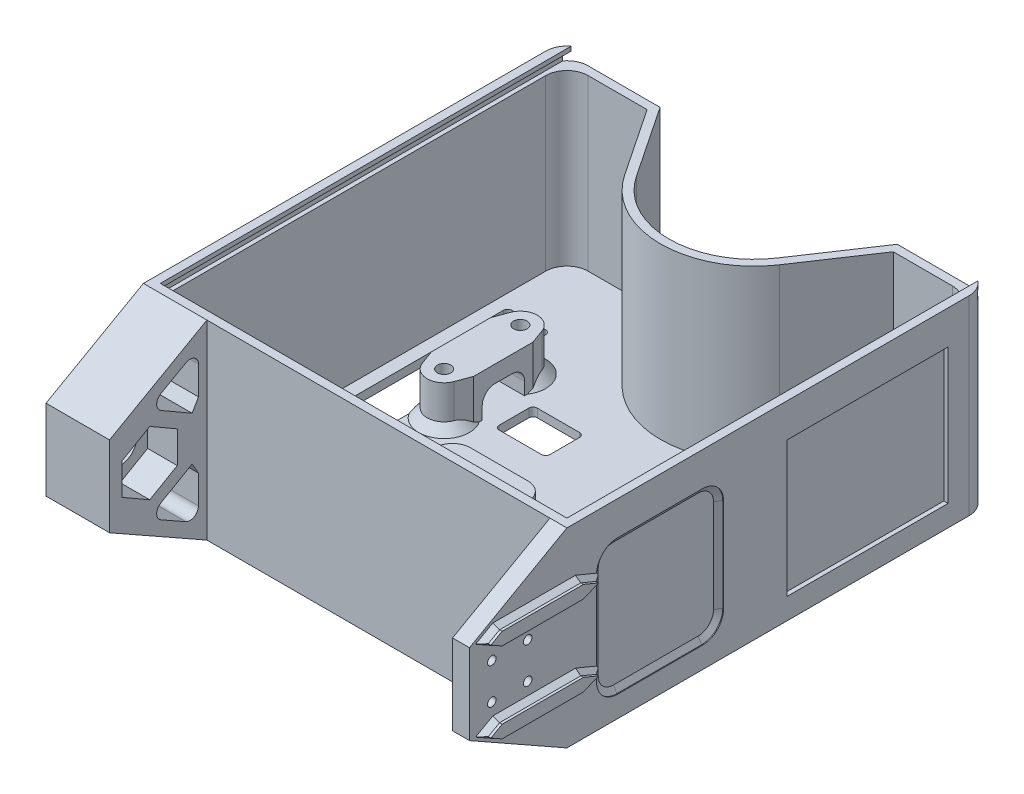
SolidWorks part; units mm, degrees
material "PVC hart"
ref_plane "Ebene vorne" through (0, 0, 0) normal (0, 0, 1) x (1, 0, 0)
ref_plane "Ebene oben" through (0, 0, 0) normal (0, 1, 0) x (1, 0, 0)
ref_plane "Ebene rechts" through (0, 0, 0) normal (1, 0, 0) x (0, 0, -1)
sketch "Grundplatte" plane through (0, 0, 0) normal (0, 1, 0) x (1, 0, 0)
  line L0 (0, 69.0751) -> (0, -94.5087) construction
  line L2 (-50, 50) -> (-50, -50)
  line L3 (-50, -50) -> (50, -50)
  line L4 (50, 50) -> (50, -50)
  line L5 (-50, 50) -> (50, -50) construction
  line L6 (-50, -50) -> (50, 50) construction
  line L7 (-50, 50) -> (-28, 50)
  line L8 (-28, 50) -> (-16.6199, 33)
  line L9 (28, 50) -> (16.6199, 33)
  line L10 (50, 50) -> (28, 50)
  arc A0 (-16.6199, 33) -> (16.6199, 33) centre (0, 44.1257) ccw
  point P0 (0, 0)
  dimension "D4" = 20
  dimension "D1" = 100
  dimension "D2" = 100
  dimension "D3" = 22
  dimension "D5" = 17
extrude "Aufsatz-Linear austragen1" add sketch "Grundplatte" along normal blind 45
shell "Wandung1" thickness 2 removed face at (0, 45, -19.6407)
sketch "Skizze1" plane through (0, 2, 0) normal (0, 1, 0) x (1, 0, 0)
  line L0 (0, 51.8201) -> (0, -55.3816) construction
  line L1 (-28, 50) -> (-50, 50) construction
  line L2 (-45, 31) -> (-35, 31)
  line L3 (-45, 31) -> (-45, -11)
  line L4 (-45, -11) -> (-35, -11)
  line L5 (-35, 31) -> (-35, -11)
  line L6 (-45, 31) -> (-35, -11) construction
  line L7 (-45, -11) -> (-35, 31) construction
  line L8 (50, 50) -> (28, 50) construction
  line L9 (35, 31) -> (45, 31)
  line L10 (35, 31) -> (35, -11)
  line L11 (35, -11) -> (45, -11)
  line L12 (45, 31) -> (45, -11)
  line L13 (35, 31) -> (45, -11) construction
  line L14 (35, -11) -> (45, 31) construction
  point P3 (-40, 10)
  point P10 (40, 10)
  dimension "D1" = 10
  dimension "D2" = 42
  dimension "D3" = 40
  dimension "D4" = 40
  dimension "D5" = 42
  dimension "D6" = 10
  dimension "D7" = 40
  dimension "D8" = 40
extrude "Schnitt-Linear austragen1" cut sketch "Skizze1" against normal up to surface (2 mm away) up to face at (0, 0, -19.6407)
sketch "Skizze2" plane through (0, 2, 0) normal (0, 1, 0) x (1, 0, 0)
  line L20 (-65.457, 10) -> (65.6069, 10) construction
  line L21 (0, 51.8201) -> (0, -54.6693) construction
  line L22 (-35, -11) -> (-35, 31) construction
  line L24 (-35, 16) -> (-35, 4)
  line L26 (-25, 16) -> (-25, 4)
  line L27 (-35, 16) -> (-25, 4) construction
  line L28 (-35, 4) -> (-25, 16) construction
  line L33 (35, 16) -> (35, 17)
  line L34 (33.7533, 20.3831) -> (35, 17)
  line L36 (-35, 16) -> (-35, 17)
  line L37 (-25, 16) -> (-25, 17)
  line L38 (-35, 4) -> (-35, 3)
  line L39 (-25, 4) -> (-25, 3)
  line L40 (-26.2467, 20.3831) -> (-25, 17)
  line L41 (-33.7533, 20.3831) -> (-35, 17)
  line L42 (-26.2467, -0.3831) -> (-25, 3)
  line L43 (-33.7533, -0.3831) -> (-35, 3)
  line L44 (26.2467, 20.3831) -> (25, 17)
  line L45 (25, 16) -> (25, 17)
  line L46 (25, 16) -> (25, 4)
  line L47 (25, 4) -> (25, 3)
  line L48 (26.2467, -0.3831) -> (25, 3)
  line L49 (33.7533, -0.3831) -> (35, 3)
  line L50 (35, 4) -> (35, 3)
  line L51 (35, 16) -> (35, 4)
  circle A4 centre (-30, 19) radius 1.6
  circle A5 centre (-30, 1) radius 1.6
  arc A6 (-26.2467, 20.3831) -> (-33.7533, 20.3831) centre (-30, 19) ccw
  arc A7 (-26.2467, -0.3831) -> (-33.7533, -0.3831) centre (-30, 1) cw
  circle A8 centre (30, 1) radius 1.6
  circle A9 centre (30, 19) radius 1.6
  arc A10 (26.2467, 20.3831) -> (33.7533, 20.3831) centre (30, 19) cw
  arc A11 (26.2467, -0.3831) -> (33.7533, -0.3831) centre (30, 1) ccw
  point P4 (-30, 10)
  point P9 (30, 10)
  dimension "D9" = 3.2
  dimension "D10" = 3.2
  dimension "D13" = 4
  dimension "D14" = 4
  dimension "D2" = 30
  dimension "D3" = 10
  dimension "D5" = 1
  dimension "D6" = 1
  dimension "D7" = 1
  dimension "D8" = 1
  dimension "D11" = 9
  dimension "D12" = 9
extrude "Aufsatz-Linear austragen2" add sketch "Skizze2" along normal blind 10
fillet "Verrundung1" radius 1 8 edges at (35, 1, -31) (45, 1, -31) (35, 1, 11) (45, 1, 11) (-35, 1, 11) (-45, 1, 11) (-45, 1, -31) (-35, 1, -31)
sketch "Skizze6" plane through (0, 12, 0) normal (0, 1, 0) x (1, 0, 0)
  circle A0 centre (-30, 19) radius 1.6
  circle A1 centre (-30, 1) radius 1.6
  circle A2 centre (30, 19) radius 1.6
  circle A3 centre (30, 1) radius 1.6
  dimension "D1" = 3.2
  dimension "D2" = 3.2
  dimension "D3" = 3.2
  dimension "D4" = 3.2
extrude "Schnitt-Linear austragen2" cut sketch "Skizze6" against normal through all
sketch "Skizze7" plane through (0, 0, 0) normal (0, -1, 0) x (1, 0, 0)
  line L0 (0, 58.5427) -> (0, -57.727) construction
  line L1 (-26.7091, -1) -> (-28.3546, 1.85)
  line L2 (-28.3546, 1.85) -> (-31.6454, 1.85)
  line L3 (-31.6454, 1.85) -> (-33.2909, -1)
  line L4 (-33.2909, -1) -> (-31.6454, -3.85)
  line L5 (-31.6454, -3.85) -> (-28.3546, -3.85)
  line L6 (-28.3546, -3.85) -> (-26.7091, -1)
  line L7 (28.3546, -21.85) -> (26.7091, -19)
  line L8 (-26.7091, -19) -> (-28.3546, -16.15)
  line L9 (-28.3546, -16.15) -> (-31.6454, -16.15)
  line L10 (-31.6454, -16.15) -> (-33.2909, -19)
  line L11 (-33.2909, -19) -> (-31.6454, -21.85)
  line L12 (-31.6454, -21.85) -> (-28.3546, -21.85)
  line L13 (-28.3546, -21.85) -> (-26.7091, -19)
  line L14 (31.6454, -21.85) -> (28.3546, -21.85)
  line L15 (33.2909, -19) -> (31.6454, -21.85)
  line L16 (31.6454, -16.15) -> (33.2909, -19)
  line L17 (28.3546, -16.15) -> (31.6454, -16.15)
  line L18 (26.7091, -19) -> (28.3546, -16.15)
  line L19 (28.3546, -3.85) -> (26.7091, -1)
  line L20 (31.6454, -3.85) -> (28.3546, -3.85)
  line L21 (33.2909, -1) -> (31.6454, -3.85)
  line L22 (31.6454, 1.85) -> (33.2909, -1)
  line L23 (28.3546, 1.85) -> (31.6454, 1.85)
  line L24 (26.7091, -1) -> (28.3546, 1.85)
  circle A0 centre (-30, -1) radius 2.85 construction
  circle A1 centre (-30, -19) radius 2.85 construction
  dimension "D1" = 5.7
  dimension "D2" = 5.7
extrude "Schnitt-Linear austragen3" cut sketch "Skizze7" against normal offset from surface (9 mm away) 3 up to face at (30, 12, -2.6)
chamfer "Fase1" distance 2 angle 45 8 edges at (34.3766, 2, -1.3084) (30, 2, 3) (34.3766, 2, -18.6916) (30, 2, -23) (-34.3766, 2, -18.6916) (-30, 2, -23) (-34.3766, 2, -1.3084) (-30, 2, 3)
sketch "Skizze8" plane through (0, 0, 0) normal (0, -1, 0) x (1, 0, 0)
  line L0 (0, 60.6503) -> (0, -60.3099) construction
  line L1 (22, -5) -> (10, -5)
  line L2 (-22, -14) -> (-10, -14)
  line L3 (-22, -14) -> (-22, -5)
  line L4 (-22, -5) -> (-10, -5)
  line L5 (-10, -14) -> (-10, -5)
  line L10 (10, -14) -> (10, -5)
  line L11 (22, -14) -> (10, -14)
  line L12 (22, -14) -> (22, -5)
  circle A0 centre (-30, -1) radius 1.6 construction
  dimension "D2" = 4
  dimension "D1" = 12
  dimension "D3" = 10
  dimension "D4" = 9
extrude "Schnitt-Linear austragen4" cut sketch "Skizze8" against normal up to surface (2 mm away) up to face at (-36.1139, 2, -10)
fillet "Verrundung2" radius 1 8 edges at (-22, 1, -14) (-22, 1, -5) (-10, 1, -5) (-10, 1, -14) (22, 1, -14) (22, 1, -5) (10, 1, -14) (10, 1, -5)
fillet "Verrundung3" radius 5 2 edges at (-50, 22.5, -50) (50, 22.5, -50)
fillet "Verrundung4" radius 5 2 edges at (48, 23.5, -48) (-48, 23.5, -48)
sketch "Skizze9" plane through (0, 0, 0) normal (0, -1, 0) x (1, 0, 0)
  line L0 (0, 55.7734) -> (0, -61.0444) construction
  line L1 (-11, -5) -> (-21, -5) construction
  line L2 (-6.8, 43) -> (6.8, 43)
  line L3 (-8, 41.8) -> (-8, 20.2)
  line L4 (-6.8, 19) -> (6.8, 19)
  line L5 (8, 41.8) -> (8, 20.2)
  line L6 (-8, 43) -> (8, 19) construction
  line L7 (-8, 19) -> (8, 43) construction
  arc A0 (6.8, 19) -> (8, 20.2) centre (6.8, 20.2) ccw
  arc A1 (-8, 20.2) -> (-6.8, 19) centre (-6.8, 20.2) ccw
  arc A2 (-6.8, 43) -> (-8, 41.8) centre (-6.8, 41.8) ccw
  arc A3 (6.8, 43) -> (8, 41.8) centre (6.8, 41.8) cw
  point P3 (0, 31)
  dimension "D4" = 1.2
  dimension "D1" = 24
  dimension "D2" = 16
  dimension "D3" = 36
extrude "Schnitt-Linear austragen5" cut sketch "Skizze9" against normal up to next
sketch "Skizze11" plane through (0, 2, 0) normal (0, 1, 0) x (1, 0, 0)
  line L25 (-6.8, -46) -> (6.8, -46)
  line L26 (-11, -20.2) -> (-11, -41.8)
  line L27 (11, -41.8) -> (11, -20.2)
  line L28 (6.8, -16) -> (-6.8, -16)
  line L29 (-6.8, -46) -> (6.8, -46)
  line L30 (-11, -20.2) -> (-11, -41.8)
  line L31 (11, -41.8) -> (11, -20.2)
  line L32 (6.8, -16) -> (-6.8, -16)
  line L62 (-8, -20.2) -> (-8, -41.8)
  line L63 (-6.8, -43) -> (6.8, -43)
  line L64 (8, -41.8) -> (8, -20.2)
  line L65 (-6.8, -19) -> (6.8, -19)
  arc A19 (6.8, -46) -> (11, -41.8) centre (6.8, -41.8) ccw
  arc A20 (-11, -41.8) -> (-6.8, -46) centre (-6.8, -41.8) ccw
  arc A21 (-6.8, -16) -> (-11, -20.2) centre (-6.8, -20.2) ccw
  arc A22 (11, -20.2) -> (6.8, -16) centre (6.8, -20.2) ccw
  arc A23 (6.8, -46) -> (11, -41.8) centre (6.8, -41.8) ccw
  arc A24 (-11, -41.8) -> (-6.8, -46) centre (-6.8, -41.8) ccw
  arc A25 (-6.8, -16) -> (-11, -20.2) centre (-6.8, -20.2) ccw
  arc A26 (11, -20.2) -> (6.8, -16) centre (6.8, -20.2) ccw
  arc A50 (-6.8, -19) -> (-8, -20.2) centre (-6.8, -20.2) ccw
  arc A51 (6.8, -19) -> (8, -20.2) centre (6.8, -20.2) cw
  arc A52 (-6.8, -43) -> (-8, -41.8) centre (-6.8, -41.8) cw
  arc A53 (6.8, -43) -> (8, -41.8) centre (6.8, -41.8) ccw
  dimension "D1" = 3
extrude "Aufsatz-Linear austragen3" add sketch "Skizze11" along normal blind 12
sketch "Skizze12" plane through (0, 14, 0) normal (0, 1, 0) x (1, 0, 0)
  line L30 (11, -41.8) -> (11, -20.2)
  line L31 (-6.8, -46) -> (6.8, -46)
  line L32 (-11, -20.2) -> (-11, -41.8)
  line L33 (6.8, -16) -> (-6.8, -16)
  line L34 (11, -41.8) -> (11, -20.2)
  line L35 (-6.8, -46) -> (6.8, -46)
  line L36 (-11, -20.2) -> (-11, -41.8)
  line L37 (6.8, -16) -> (-6.8, -16)
  arc A14 (6.8, -46) -> (11, -41.8) centre (6.8, -41.8) ccw
  arc A15 (-11, -41.8) -> (-6.8, -46) centre (-6.8, -41.8) ccw
  arc A16 (-6.8, -16) -> (-11, -20.2) centre (-6.8, -20.2) ccw
  arc A17 (11, -20.2) -> (6.8, -16) centre (6.8, -20.2) ccw
  arc A18 (6.8, -46) -> (11, -41.8) centre (6.8, -41.8) ccw
  arc A19 (-11, -41.8) -> (-6.8, -46) centre (-6.8, -41.8) ccw
  arc A20 (-6.8, -16) -> (-11, -20.2) centre (-6.8, -20.2) ccw
  arc A21 (11, -20.2) -> (6.8, -16) centre (6.8, -20.2) ccw
  dimension "D1" = 3
extrude "Aufsatz-Linear austragen4" add sketch "Skizze12" along normal blind 2
chamfer "Fase2" distance 2 angle 45 8 edges at (-11, 2, 31) (-9.7698, 2, 44.7698) (-9.7698, 2, 17.2302) (0, 2, 46) (0, 2, 16) (9.7698, 2, 44.7698) (9.7698, 2, 17.2302) (11, 2, 31)
sketch "Skizze13" plane through (0, 16, 0) normal (0, 1, 0) x (1, 0, 0)
  line L0 (0, 40.7845) -> (0, -65.4996) construction
  line L1 (-15.9895, -31) -> (16.789, -31) construction
  line L2 (6.8, -16) -> (-6.8, -16) construction
  line L3 (-6.8, -46) -> (6.8, -46) construction
  circle A0 centre (0, -23) radius 1.6
  circle A1 centre (0, -39) radius 1.6
  dimension "D1" = 3.2
  dimension "D2" = 3.2
  dimension "D3" = 16
extrude "Schnitt-Linear austragen6" cut sketch "Skizze13" along direction (0, 1, 0) on the side against the normal up to surface (2 mm away) up to face at (0, 14, 31)
sketch "Skizze14" plane through (0, 0, 50) normal (0, 0, 1) x (1, 0, 0)
  line L0 (0, 49.837) -> (0, -24.1023) construction
  line L1 (-50, 45) -> (-50, 0)
  line L2 (-50, 0) -> (-35, 0)
  line L3 (-50, 0) -> (50, 0) construction
  line L4 (-35, 0) -> (-35, 45)
  line L5 (-50, 45) -> (50, 45) construction
  line L6 (-35, 45) -> (-50, 45)
  line L7 (50, 45) -> (46, 45)
  line L8 (46, 45) -> (46, 0)
  line L9 (46, 0) -> (50, 0)
  line L10 (50, 0) -> (50, 45)
  dimension "D1" = 15
  dimension "D2" = 4
extrude "Aufsatz-Linear austragen5" add sketch "Skizze14" along normal blind 23
sketch "Skizze18" plane through (50, 0, 0) normal (1, 0, 0) x (0, 0, -1)
  line L0 (-50, 46.4423) -> (-50, -7.8316) construction
  line L1 (-73, 0) -> (-73, 45) construction
  line L3 (-73, 0) -> (45, 0) construction
  circle A0 centre (-63.5, 22.5) radius 6 construction
  circle A5 centre (-59.2574, 18.2574) radius 1
  circle A9 centre (-67.7426, 18.2574) radius 1
  circle A11 centre (-67.7426, 26.7426) radius 1
  circle A13 centre (-59.2574, 26.7426) radius 1
  point P27 (-63.5, 22.5)
  point P28 (-63.5, 22.5)
  dimension "D2" = 12
  dimension "D5" = 2
  dimension "D6" = 2
  dimension "D7" = 2
  dimension "D8" = 2
  dimension "D1" = 23
  dimension "D3" = 13.5
  dimension "D4" = 22.5
extrude "Schnitt-Linear austragen8" cut sketch "Skizze18" against normal up to surface (4 mm away) up to face at (46, 22.5, 61.5)
sketch "Skizze19" plane through (46, 0, 0) normal (-1, 0, 0) x (0, 0, 1)
  line L0 (50, 40.9842) -> (50, -6.1788) construction
  line L1 (73, 45) -> (73, 0) construction
  line L2 (73, 45) -> (50, 45) construction
  circle A0 centre (63.5, 22.5) radius 2.5
  dimension "D2" = 5
  dimension "D1" = 23
  dimension "D3" = 13.5
  dimension "D4" = 22.5
extrude "Schnitt-Linear austragen9" cut sketch "Skizze19" against normal blind 2.5
sketch "Skizze20" plane through (0, 0, 50) normal (0, 0, 1) x (1, 0, 0)
  line L0 (46, 45) -> (46, 0) construction
  line L1 (41, 27.5) -> (46, 27.5)
  line L2 (41, 27.5) -> (41, 17.5)
  line L3 (41, 17.5) -> (46, 17.5)
  line L4 (46, 27.5) -> (46, 17.5)
  line L5 (41, 27.5) -> (46, 17.5) construction
  line L6 (41, 17.5) -> (46, 27.5) construction
  line L7 (-35, 45) -> (46, 45) construction
  point P0 (43.5, 22.5)
  dimension "D1" = 10
  dimension "D2" = 5
  dimension "D3" = 22.5
extrude "Schnitt-Linear austragen10" cut sketch "Skizze20" against normal up to surface (2 mm away) up to face at (0, 16.3333, 48)
sketch "Skizze21" plane through (-50, 0, 0) normal (-1, 0, 0) x (0, 0, 1)
  line L0 (50, 45.8781) -> (50, -12.9091) construction
  line L1 (73, 45) -> (73, 0) construction
  line L2 (-45, 45) -> (73, 45) construction
  circle A0 centre (63.5, 22.5) radius 4
  dimension "D4" = 8
  dimension "D1" = 23
  dimension "D2" = 13.5
  dimension "D3" = 22.5
extrude "Schnitt-Linear austragen11" cut sketch "Skizze21" against normal up to surface (15 mm away) contours A0 up to face at (-35, 22.5, 61.5)
sketch "Skizze23" plane through (-50, 0, 0) normal (-1, 0, 0) x (0, 0, 1)
  circle A0 centre (63.5, 22.5) radius 7.5
  dimension "D1" = 15
extrude "Schnitt-Linear austragen12" cut sketch "Skizze23" against normal blind 1
sketch "Skizze24" plane through (-49, 0, 0) normal (-1, 0, 0) x (0, 0, 1)
  circle A0 centre (63.5, 22.5) radius 7.5
  dimension "D1" = 15
extrude "Schnitt-Linear austragen13" cut sketch "Skizze24" against normal blind 4 draft 45
sketch "Skizze26" plane through (-35, 0, 0) normal (1, 0, 0) x (0, 0, -1)
  line L0 (-73, 0) -> (-73, 45) construction
  line L1 (-57, 18.7472) -> (-57, 26.2528)
  line L2 (-57, 26.2528) -> (-63.5, 30.0056)
  line L3 (-63.5, 30.0056) -> (-70, 26.2528)
  line L4 (-70, 26.2528) -> (-70, 18.7472)
  line L5 (-70, 18.7472) -> (-63.5, 14.9944)
  line L6 (-63.5, 14.9944) -> (-57, 18.7472)
  circle A0 centre (-63.5, 22.5) radius 6.5 construction
  dimension "D1" = 13
extrude "Schnitt-Linear austragen14" cut sketch "Skizze26" against normal blind 7
sketch "Skizze29" plane through (-50, 0, 0) normal (-1, 0, 0) x (0, 0, 1)
  line L0 (50, 50.1212) -> (50, -3.8482) construction
  line L1 (73, 45) -> (73, 0) construction
  line L2 (73, 45) -> (73, 32)
  line L3 (73, 32) -> (50, 45)
  line L4 (50, 45) -> (73, 45)
  dimension "D1" = 23
  dimension "D2" = 13
extrude "Schnitt-Linear austragen15" cut sketch "Skizze29" against normal up to surface (100 mm away) up to face at (50, 26.7426, 58.2574)
sketch "Skizze31" plane through (0, 0, -50) normal (0, 0, -1) x (-1, 0, 0)
  line L0 (-48, 45) -> (-48, 42)
  line L1 (-45, 45) -> (-50, 45) construction
  line L2 (-48, 42) -> (48, 42)
  line L3 (48, 42) -> (48, 45)
  line L4 (50, 45) -> (45, 45) construction
  line L5 (48, 45) -> (-48, 45)
  line L6 (-50, 0) -> (-50, 45) construction
  line L7 (50, 45) -> (50, 0) construction
  dimension "D1" = 2
  dimension "D2" = 2
  dimension "D3" = 3
extrude "Schnitt-Linear austragen16" cut sketch "Skizze31" against normal blind 30
sketch "Skizze32" plane through (0, 0, -50) normal (0, 0, -1) x (-1, 0, 0)
  line L0 (-48, 45) -> (-50, 45) construction
  line L2 (-49, 44) -> (-49, 42)
  line L3 (-49, 42) -> (49, 42)
  line L4 (49, 42) -> (49, 44)
  line L5 (49, 44) -> (-49, 44)
  line L6 (-50, 0) -> (-50, 45) construction
  line L7 (50, 45) -> (50, 0) construction
  dimension "D1" = 1
  dimension "D2" = 3
  dimension "D3" = 1
  dimension "D4" = 1
extrude "Schnitt-Linear austragen17" cut sketch "Skizze32" against normal blind 99
sketch "Skizze33" plane through (50, 0, 0) normal (1, 0, 0) x (0, 0, -1)
  line L0 (-50, 51.8362) -> (-50, -5.0941) construction
  line L1 (-73, 0) -> (-73, 32) construction
  line L2 (-50, 0) -> (-73, 13)
  line L3 (-73, 13) -> (-73, 0)
  line L4 (-73, 0) -> (-50, 0)
  dimension "D1" = 23
  dimension "D2" = 13
extrude "Schnitt-Linear austragen18" cut sketch "Skizze33" against normal up to surface (100 mm away) up to face at (-50, 22.5, 71)
sketch "Skizze34" plane through (25, 0, 0) normal (-1, 0, 0) x (0, 0, 1)
  line L0 (-10, 2) -> (-10, 12) construction
  line L1 (-15.6834, 2) -> (-4.3166, 2) construction
  line L2 (-17, 12) -> (-3, 12) construction
  line L3 (-5, 2) -> (-15, 2)
  line L4 (-15, 2) -> (-15, 8)
  line L5 (-15, 8) -> (-5, 8)
  line L6 (-5, 2) -> (-5, 8)
  point P11 (-10, 8)
  dimension "D1" = 10
  dimension "D2" = 6
extrude "Schnitt-Linear austragen19" cut sketch "Skizze34" against normal up to next and the other way up to surface other way up to face at (-35, 3.7785, -9.8772)
fillet "Verrundung5" radius 3 4 edges at (-30, 8, -15) (-30, 8, -5) (30, 8, -5) (30, 8, -15)
sketch "Skizze35" plane through (50, 0, 0) normal (1, 0, 0) x (0, 0, -1)
  line L0 (-50, 0) -> (45, 0) construction
  line L1 (-43, 37) -> (-13, 37)
  line L2 (-43, 37) -> (-43, 5)
  line L3 (-43, 5) -> (-13, 5)
  line L4 (-13, 37) -> (-13, 5)
  line L5 (2, 37) -> (40, 37)
  line L6 (2, 37) -> (2, 5)
  line L7 (2, 5) -> (40, 5)
  line L8 (40, 37) -> (40, 5)
  line L9 (-50, 45) -> (45, 45) construction
  line L10 (-73, 13) -> (-73, 32) construction
  line L11 (50, 42) -> (50, 0) construction
  dimension "D1" = 5
  dimension "D2" = 8
  dimension "D3" = 30
  dimension "D4" = 15
  dimension "D5" = 10
  dimension "D6" = 30
extrude "Schnitt-Linear austragen20" cut sketch "Skizze35" against normal offset from surface (1 mm away) 1 up to face at (48, 22, 2.5)
fillet "Verrundung6" radius 5 4 edges at (49.5, 5, 43) (49.5, 5, 13) (49.5, 37, 13) (49.5, 37, 43)
chamfer "Fase3" distance 0.8 angle 60 8 edges at (49, 35.5355, 41.5355) (49, 37, 28) (49, 35.5355, 14.4645) (49, 21, 13) (49, 6.4645, 14.4645) (49, 5, 28) (49, 6.4645, 41.5355) (49, 21, 43) first distance on face at (49.5, 35.0178, 41.0178) first distance on face at (49.5, 37, 28) first distance on face at (49.5, 35.0178, 14.9822) first distance on face at (49.5, 21, 13) first distance on face at (49.5, 6.9822, 14.9822) first distance on face at (49.5, 5, 28) first distance on face at (49.5, 6.9822, 41.0178) first distance on face at (49.5, 21, 43)
sketch "Skizze37" plane through (-35, 0, 0) normal (1, 0, 0) x (0, 0, -1)
  line L0 (-52, 40.4235) -> (-63.8972, 33.699)
  line L1 (-63.8972, 33.699) -> (-53.5, 27.6962)
  line L2 (-53.5, 27.6962) -> (-52, 30.2942)
  line L3 (-52, 30.2942) -> (-52, 40.4235)
  line L8 (-73, 22.5) -> (-50, 22.5) construction
  line L9 (-73, 13) -> (-73, 32) construction
  line L10 (-50, 0) -> (-50, 45) construction
  line L11 (-50, 45) -> (-73, 32) construction
  line L12 (-57, 26.2528) -> (-63.5, 30.0056) construction
  line L13 (-52, 14.7058) -> (-52, 4.5765)
  line L14 (-53.5, 17.3038) -> (-52, 14.7058)
  line L15 (-63.8972, 11.301) -> (-53.5, 17.3038)
  line L16 (-52, 4.5765) -> (-63.8972, 11.301)
  dimension "D1" = 2
  dimension "D2" = 3
  dimension "D3" = 3
  dimension "D4" = 3
extrude "Schnitt-Linear austragen21" cut sketch "Skizze37" against normal offset from surface (13 mm away) 2 up to face at (-50, 22.5, 71)
fillet "Verrundung7" radius 2 4 edges at (-41.5, 4.5765, 52) (-41.5, 11.301, 63.8972) (-41.5, 33.699, 63.8972) (-41.5, 40.4235, 52)
sketch "Skizze38" plane through (50, 0, 0) normal (1, 0, 0) x (0, 0, -1)
  line L0 (-73, 22.5) -> (50, 22.5) construction
  line L1 (-73, 13) -> (-73, 32) construction
  line L2 (50, 42) -> (50, 0) construction
  line L3 (-73, 32) -> (-43, 32) construction
  line L4 (-69.9516, 32) -> (-67.2977, 33.5)
  line L5 (-67.2977, 33.5) -> (-48.1213, 33.5)
  line L6 (-48.1213, 33.5) -> (-44.5, 32)
  line L7 (-73, 32) -> (-50, 45) construction
  line L8 (-48.1213, 30.5) -> (-44.5, 32)
  line L9 (-67.2977, 30.5) -> (-48.1213, 30.5)
  line L10 (-69.9516, 32) -> (-67.2977, 30.5)
  line L11 (-43, 10) -> (-43, 32) construction
  line L12 (-73, 13) -> (-43, 13) construction
  line L13 (-69.9516, 13) -> (-67.2977, 14.5)
  line L14 (-67.2977, 14.5) -> (-48.1213, 14.5)
  line L15 (-48.1213, 14.5) -> (-44.5, 13)
  line L16 (-48.1213, 11.5) -> (-44.5, 13)
  line L17 (-67.2977, 11.5) -> (-48.1213, 11.5)
  line L18 (-69.9516, 13) -> (-67.2977, 11.5)
  dimension "D1" = 3
  dimension "D2" = 1.5
  dimension "D3" = 1.5
  dimension "D4" = 45
extrude "Aufsatz-Linear austragen6" add sketch "Skizze38" along normal blind 2
chamfer "Fase4" distance 0.8 angle 60 12 edges at (50, 13.75, 68.6247) (50, 12.25, 68.6247) (50, 11.5, 57.7095) (50, 12.25, 46.3107) (50, 14.5, 57.7095) (50, 13.75, 46.3107) (50, 32.75, 46.3107) (50, 31.25, 46.3107) (50, 30.5, 57.7095) (50, 31.25, 68.6247) (50, 32.75, 68.6247) (50, 33.5, 57.7095) first distance on face at (50, 32, 57.5483)
